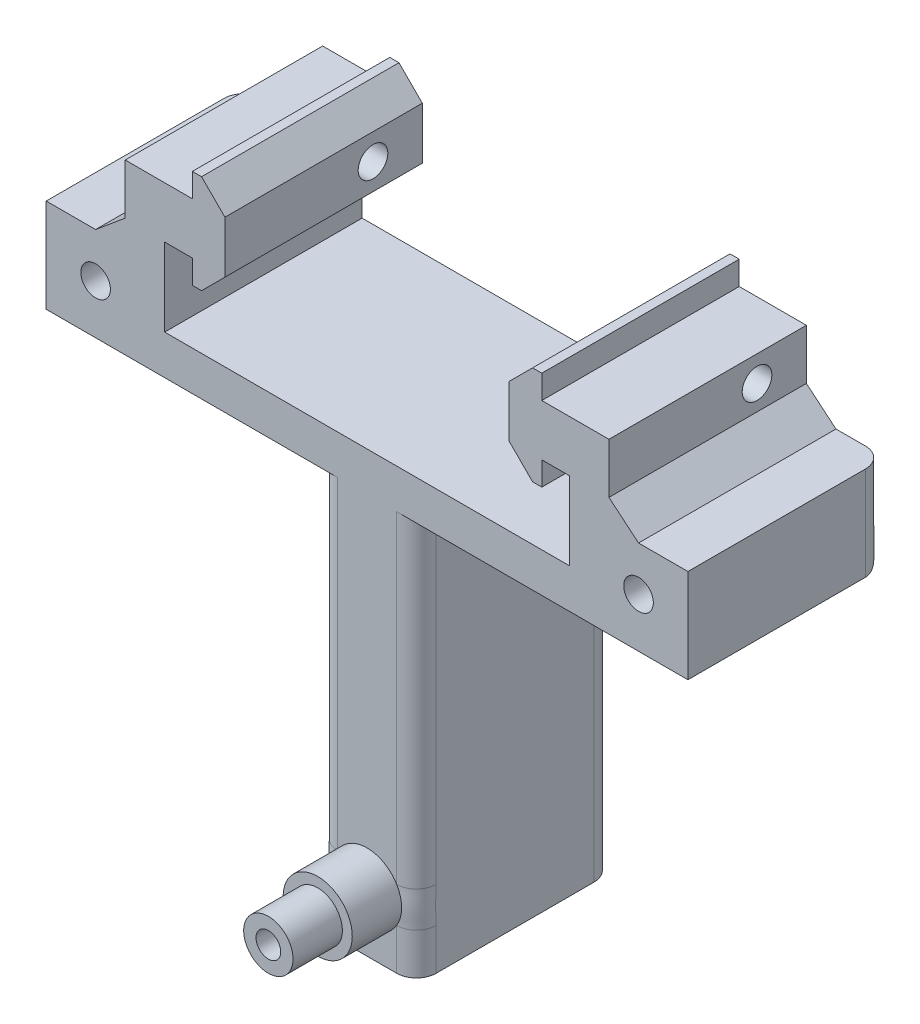
SolidWorks part; units mm, degrees
ref_plane "Front Plane" through (0, 0, 0) normal (0, 0, 1) x (1, 0, 0)
ref_plane "Top Plane" through (0, 0, 0) normal (0, 1, 0) x (1, 0, 0)
ref_plane "Right Plane" through (0, 0, 0) normal (1, 0, 0) x (0, 0, -1)
sketch "Sketch1" plane through (0, 0, 0) normal (0, 0, 1) x (1, 0, 0)
  line L0 (-14.5, 2.6) -> (-7.7, 2.6)
  line L1 (-7.7, 2.6) -> (-7.7, 5)
  line L2 (-7.7, 5) -> (-6.7678, 5)
  line L3 (-6.7678, 5) -> (-4.4, 2.6322)
  line L4 (-4.4, 2.6322) -> (-4.4, -2.6322)
  line L5 (-4.4, -2.6322) -> (-6.7678, -5)
  line L6 (-6.7678, -5) -> (-7.7, -5)
  line L7 (-7.7, -5) -> (-7.7, -2.6)
  line L8 (-7.7, -2.6) -> (-10.5, -2.6)
  line L9 (-10.5, -2.6) -> (-10.5, -10.5)
  line L10 (-10.5, -10.5) -> (30.5, -10.5)
  line L12 (5, -55) -> (15, -55)
  line L16 (-14.5, 2.6) -> (-14.5, -14.5)
  line L17 (-3.9, 2.7565) -> (-3.9, -2.7565) construction
  line L18 (-3.9586, -2.8979) -> (-6.5607, -5.5) construction
  line L19 (-3.9586, 2.8979) -> (-6.5607, 5.5) construction
  line L20 (-6.5607, 5.5) -> (-8, 5.5) construction
  line L21 (-8.2, 5.3) -> (-8.2, 3.1) construction
  line L22 (-8.2, 3.1) -> (-9.3, 3.1) construction
  line L23 (-8.2, -5.3) -> (-8.2, -3.1) construction
  line L24 (-6.5607, -5.5) -> (-8, -5.5) construction
  line L25 (-8.2, -3.1) -> (-9.3, -3.1) construction
  line L26 (-10, -3.8) -> (-10, -8.5) construction
  line L27 (-14.5, -14.5) -> (5, -14.5)
  line L28 (10, 10) -> (10, -10) construction
  line L29 (-8.5, -10) -> (-3.8, -10) construction
  line L30 (5, -14.5) -> (5, -55)
  line L31 (3.8, -10) -> (8.5, -10) construction
  line L34 (8.5, 10) -> (11.5, 10) construction
  line L35 (8.5, -10) -> (11.5, -10) construction
  line L36 (30.5, -2.6) -> (30.5, -10.5)
  line L37 (27.7, -2.6) -> (30.5, -2.6)
  line L38 (27.7, -5) -> (27.7, -2.6)
  line L39 (26.7678, -5) -> (27.7, -5)
  line L40 (24.4, -2.6322) -> (26.7678, -5)
  line L41 (24.4, 2.6322) -> (24.4, -2.6322)
  line L42 (26.7678, 5) -> (24.4, 2.6322)
  line L43 (27.7, 5) -> (26.7678, 5)
  line L44 (27.7, 2.6) -> (27.7, 5)
  line L45 (34.5, 2.6) -> (27.7, 2.6)
  line L46 (34.5, 2.6) -> (34.5, -14.5)
  line L47 (34.5, -14.5) -> (15, -14.5)
  line L48 (15, -14.5) -> (15, -55)
  dimension "D1" = 0.5
  dimension "D2" = 0.5
  dimension "D3" = 0.5
  dimension "D4" = 0.5
  dimension "D5" = 0.5
  dimension "D6" = 0.5
  dimension "D7" = 0.5
  dimension "D8" = 0.5
  dimension "D9" = 0.5
  dimension "D10" = 0.5
  dimension "D11" = 4
  dimension "D12" = 0.5
  dimension "D13" = 4
  dimension "D14" = 5
  dimension "D16" = 45
extrude "Boss-Extrude1" add sketch "Sketch1" along normal blind 20
sketch "Sketch2" plane through (-14.5, 0, 0) normal (-1, 0, 0) x (0, 0, 1)
  line L0 (0, 2.6) -> (0, -14.5) construction
  line L4 (20, -2.6322) -> (20, 2.6322) construction
  circle A0 centre (5, 0) radius 1.5
  point P7 (20, 0)
  dimension "D1" = 5
  dimension "D2" = 3
  dimension "D3" = 0
extrude "Cut-Extrude1" cut sketch "Sketch2" against normal blind 60
sketch "Sketch4" plane through (0, 0, 20) normal (0, 0, 1) x (1, 0, 0)
  line L0 (5, -55) -> (15, -55) construction
  line L1 (30.5, -10.5) -> (-10.5, -10.5) construction
  circle A0 centre (10, -49) radius 2.5
  point P4 (10, -55)
  dimension "D1" = 0
  dimension "D2" = 38.5
  dimension "D3" = 5
extrude "Boss-Extrude2" add sketch "Sketch4" along normal blind 10
sketch "Sketch5" plane through (0, 0, 20) normal (0, 0, 1) x (1, 0, 0)
  circle A1 centre (10, -49) radius 3.5
  dimension "D1" = 7
extrude "Boss-Extrude3" add sketch "Sketch5" along normal blind 5
sketch "Sketch6" plane through (0, 0, 30) normal (0, 0, 1) x (1, 0, 0)
  circle A0 centre (10, -49) radius 1.25
  dimension "D1" = 2.5
extrude "Cut-Extrude3" cut sketch "Sketch6" against normal blind 4
sketch "Sketch7" plane through (-14.5, 0, 0) normal (-1, 0, 0) x (0, 0, 1)
  line L0 (20, 2.6) -> (20, -14.5) construction
  line L1 (0, -14.5) -> (20, -14.5)
  line L2 (0, -14.5) -> (0, -5)
  line L3 (0, -5) -> (20, -5)
  line L4 (20, -14.5) -> (20, -5)
  circle A0 centre (5, 0) radius 1.5 construction
  dimension "D1" = 5
extrude "Boss-Extrude4" add sketch "Sketch7" along normal blind 8
sketch "Sketch8" plane through (34.5, 0, 0) normal (1, 0, 0) x (0, 0, -1)
  line L0 (-20, -14.5) -> (-20, 2.6) construction
  line L1 (0, -14.5) -> (-20, -14.5)
  line L2 (0, -14.5) -> (0, -5)
  line L3 (0, -5) -> (-20, -5)
  line L4 (-20, -14.5) -> (-20, -5)
  circle A0 centre (-5, 0) radius 1.5 construction
  dimension "D1" = 5
extrude "Boss-Extrude5" add sketch "Sketch8" along normal blind 8
sketch "Sketch9" plane through (0, 0, 20) normal (0, 0, 1) x (1, 0, 0)
  line L0 (-22.5, -14.5) -> (-22.5, -5) construction
  line L1 (-22.5, -14.5) -> (5, -14.5) construction
  line L2 (15, -14.5) -> (42.5, -14.5) construction
  line L3 (42.5, -5) -> (42.5, -14.5) construction
  circle A0 centre (-17.5, -9.5) radius 1.5
  circle A1 centre (37.5, -9.5) radius 1.5
  dimension "D1" = 3
  dimension "D2" = 5
  dimension "D3" = 5
  dimension "D4" = 5
  dimension "D5" = 3
  dimension "D6" = 5
extrude "Cut-Extrude4" cut sketch "Sketch9" against normal blind 10
fillet "Fillet1" radius 2 8 edges at (42.5, -9.75, 0) (28.75, -14.5, 0) (-22.5, -9.75, 0) (-8.75, -14.5, 0) (15, -34.75, 0) (15, -34.75, 20) (5, -34.75, 0) (5, -34.75, 20)
sketch "Sketch10" plane through (0, 0, 20) normal (0, 0, 1) x (1, 0, 0)
  line L0 (-14.5, -5) -> (-14.5, -2.5)
  line L1 (-14.5, 2.6) -> (-14.5, -5) construction
  line L2 (-14.5, -2.5) -> (-17.5, -5)
  line L3 (-22.5, -5) -> (-14.5, -5) construction
  line L4 (-17.5, -5) -> (-14.5, -5)
  line L5 (34.5, -5) -> (34.5, -2.5)
  line L6 (34.5, -5) -> (34.5, 2.6) construction
  line L7 (34.5, -2.5) -> (37.5, -5)
  line L8 (42.5, -5) -> (34.5, -5) construction
  line L9 (37.5, -5) -> (34.5, -5)
  dimension "D1" = 3
  dimension "D2" = 2.5
  dimension "D3" = 3
  dimension "D4" = 2.5
extrude "Boss-Extrude6" add sketch "Sketch10" against normal up to vertex (20 mm away) up to point (34.5, -5, 0)
